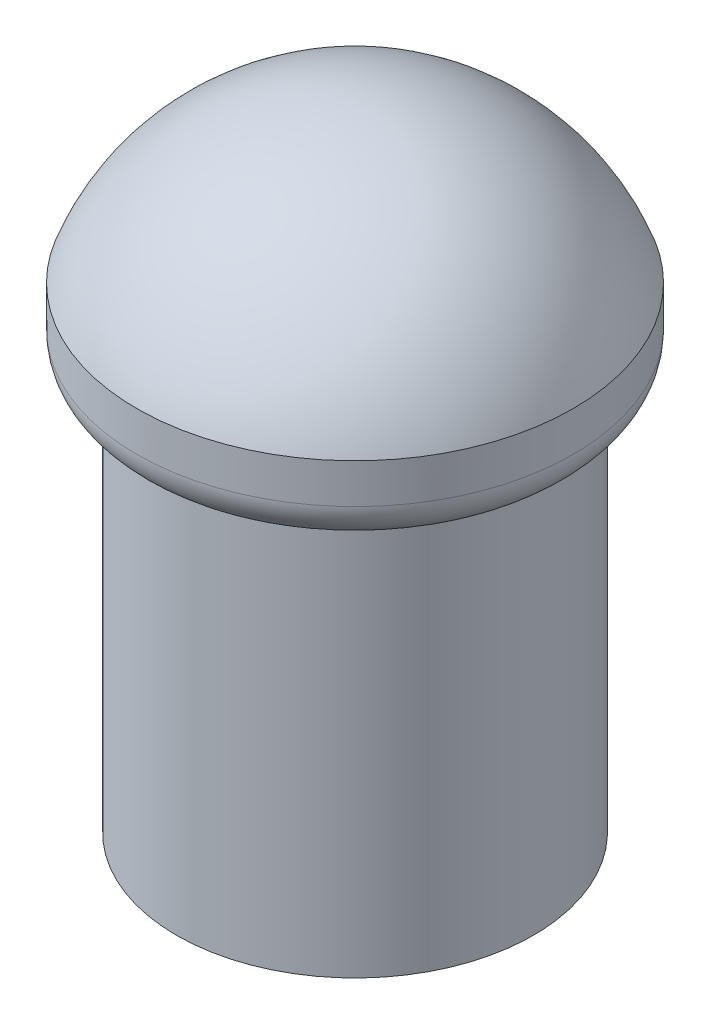
SolidWorks part; units mm, degrees
ref_plane "Front Plane" through (0, 0, 0) normal (0, 0, 1) x (1, 0, 0)
ref_plane "Top Plane" through (0, 0, 0) normal (0, 1, 0) x (1, 0, 0)
ref_plane "Right Plane" through (0, 0, 0) normal (1, 0, 0) x (0, 0, -1)
sketch "Sketch1" plane through (0, 0, 0) normal (0, 1, 0) x (1, 0, 0)
  circle A0 centre (0, 0) radius 2.25
  dimension "D1" = 4.5
extrude "Boss-Extrude1" add sketch "Sketch1" along normal blind 5
sketch "Sketch2" plane through (0, 0, 0) normal (0, 0, 1) x (1, 0, 0)
  line L0 (0, -2.0405) -> (0, 1.0153) construction
  line L1 (2.25, 5) -> (-2.25, 5) construction
  line L3 (-2.75, 6) -> (-2.75, 5)
  line L4 (-2.75, 5) -> (0, 5)
  line L7 (-2.75, 5) -> (0, 5) construction
  line L8 (0, 7.9262) -> (0, 5)
  arc A0 (0, 7.9262) -> (-2.75, 6) centre (0, 5) ccw
  point P7 (0, 5)
  point P8 (0, 4.7249)
  point P11 (0, 4.7114)
  dimension "D1" = 1
  dimension "D2" = 5.5
revolve "Revolve1" add sketch "Sketch2" angle 360 about L0
fillet "Fillet1" radius 0.5 1 edges at (0, 5, -2.75)
